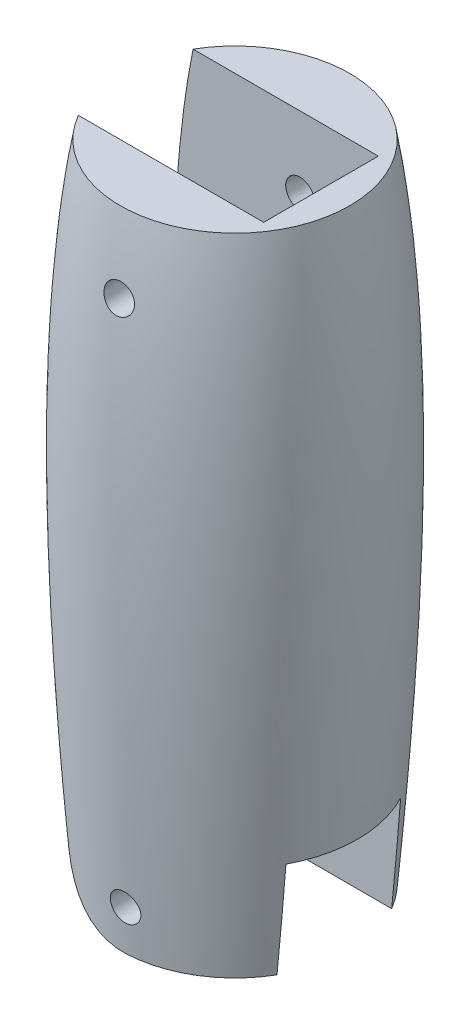
SolidWorks part; units mm, degrees
ref_plane "Front Plane" through (0, 0, 0) normal (0, 0, 1) x (1, 0, 0)
ref_plane "Top Plane" through (0, 0, 0) normal (0, 1, 0) x (1, 0, 0)
ref_plane "Right Plane" through (0, 0, 0) normal (1, 0, 0) x (0, 0, -1)
sketch "Sketch1" plane through (0, 0, 0) normal (1, 0, 0) x (0, 0, -1)
  line L0 (0, 22.5) -> (0, -22.5)
  line L1 (0, 22.5) -> (8, 22.5)
  line L2 (0, -22.5) -> (8, -22.5)
  line L3 (13.2094, -7.0442) -> (2.7906, 52.0442) construction
  spline S0 degree 2 poles (8, 22.5) (10.6047, 7.7279) (8, -22.5) knots 0 0 0 1 1 1
  point P3 (0, 0)
  dimension "D3" = 100
  dimension "D4" = 30
  dimension "D1" = 45
  dimension "D2" = 8
revolve "Revolve1" add sketch "Sketch1" angle 360 about L0
sketch "Sketch2" plane through (0, 0, 0) normal (1, 0, 0) x (0, 0, -1)
  line L0 (8, 22.5) -> (-8, 22.5) construction
  line L1 (-4, 9.5) -> (4, 9.5)
  line L2 (-4, 9.5) -> (-4, 22.5)
  line L3 (-4, 22.5) -> (4, 22.5)
  line L4 (4, 9.5) -> (4, 22.5)
  line L5 (-8, -22.5) -> (8, -22.5) construction
  line L6 (-4, -22.5) -> (4, -22.5)
  line L7 (-4, -22.5) -> (-4, -10.5)
  line L8 (-4, -10.5) -> (4, -10.5)
  line L9 (4, -22.5) -> (4, -10.5)
  point P12 (0, -10.5)
  point P14 (0, 9.5)
  dimension "D1" = 8
  dimension "D2" = 12
  dimension "D3" = 13
extrude "Cut-Extrude1" cut sketch "Sketch2" against normal through all and the other way blind 6
sketch "Sketch3" plane through (0, 0, 0) normal (0, 0, 1) x (1, 0, 0)
  line L0 (0.5359, -22.5) -> (0.5359, -19.5) construction
  line L1 (-6.9282, -22.5) -> (8, -22.5) construction
  line L2 (0.5359, 22.5) -> (0.5359, 17.5) construction
  line L3 (8, 22.5) -> (-6.9282, 22.5) construction
  circle A0 centre (0.5359, 17.5) radius 1
  circle A1 centre (0.5359, -19.5) radius 1
  dimension "D3" = 2
  dimension "D1" = 3
  dimension "D2" = 5
extrude "Cut-Extrude2" cut sketch "Sketch3" against normal through all and the other way through all
sketch "Sketch5" plane through (0, 0, 0) normal (0, 0, 1) x (1, 0, 0)
  line L2 (-6.9282, -22.5) -> (8, -22.5) construction
  line L3 (-6.9282, -22.5) -> (8, -22.5)
  line L4 (8, 22.5) -> (-6.9282, 22.5) construction
  line L5 (8, 22.5) -> (-6.9282, 22.5)
  arc A0 (-7.9472, 15.2138) -> (0.0209, 22.5) centre (0.0209, 14.5) cw
  arc A1 (0.9285, 22.5) -> (8.9036, 15.1307) centre (0.9285, 14.5) cw
  arc A2 (-7.5842, -15.1207) -> (0.3916, -22.5) centre (0.3916, -14.5) ccw
  spline S0 degree 2 poles (-501.1698, -1956.0965) (648.0055, 1954.765) (-789.8436, -1809.749) knots -9.398976 -9.398976 -9.398976 12.885608 12.885608 12.885608 only from (8, -22.5) to (8, 22.5) construction
  spline S1 degree 3 poles (1845.8539, 680.6997) (-1962.1388, -30.0919) (1945.6148, -109.903) (-1797.8674, -815.4189) knots -44.668115 -44.668115 -44.668115 -44.668115 54.513704 54.513704 54.513704 54.513704 only from (-7.9095, -10.5) to (-6.9282, -22.5) construction
  spline S3 degree 3 poles (-7.9095, -10.5) (-7.658, -14.5062) (-7.3256, -18.5058) (-6.9282, -22.5) knots 0 0 0 0 1 1 1 1
  spline S4 degree 3 poles (1845.8539, 680.6997) (-1962.1388, -30.0919) (1945.6148, -109.903) (-1797.8674, -815.4189) knots -44.668115 -44.668115 -44.668115 -44.668115 54.513704 54.513704 54.513704 54.513704 only from (-7.9095, -10.5) to (-6.9282, -22.5) construction
  spline S5 degree 3 poles (-7.9095, -10.5) (-7.658, -14.5062) (-7.3256, -18.5058) (-6.9282, -22.5) knots 0 0 0 0 1 1 1 1
  spline S6 degree 3 poles (-1999.434, -65.0382) (131.4144, -192.7145) (-17.3547, -79.9996) (-7.7636, 17.1112) (-7.6361, 18.1931) (0.9101, 77.9576) (88.0175, 128.3423) (1990.3265, -12.6904) knots -21.644551 -21.644551 -21.644551 -21.644551 0.5 0.5 0.75 0.75 14.345811 14.345811 14.345811 14.345811 only from (-8.2991, 9.5) to (-6.9282, 22.5) construction
  spline S7 degree 2 poles (8, -22.5) (10.6047, 7.7279) (8, 22.5) knots 0 0 0 1 1 1
  spline S8 degree 3 poles (-8.2991, 9.5) (-8.2182, 11.6822) (-8.0848, 13.8589) (-7.7636, 17.1112) (-7.6361, 18.1931) (-7.3275, 20.3513) (-7.1465, 21.4276) (-6.9282, 22.5) knots 0 0 0 0 0.5 0.5 0.75 0.75 1 1 1 1
  dimension "D1" = 8
  dimension "D2" = 8
extrude "Cut-Extrude4" cut sketch "Sketch5" against normal blind 20 from offset 10 contours A2 S5 L3 region at (-5.4723, -20.874, 0)
sketch "Sketch7" plane through (0, 9.5, 0) normal (0, 1, 0) x (1, 0, 0)
  circle A0 centre (-3, 0) radius 0.5
  circle A1 centre (4, 0) radius 0.5
  dimension "D1" = 1
  dimension "D2" = 1
  dimension "D3" = 3
  dimension "D4" = 4
extrude "Cut-Extrude5" cut sketch "Sketch7" against normal through all
sketch "Sketch8" plane through (6, 0, 0) normal (-1, 0, 0) x (0, 0, 1)
  line L0 (3.9999, -15.1207) -> (4, -22.5) construction
  line L1 (-4, -22.5) -> (3.9999, -22.5)
  line L2 (-4, -22.5) -> (-4, -15.5)
  line L3 (-4, -15.5) -> (3.9999, -15.5)
  line L4 (3.9999, -22.5) -> (3.9999, -15.5)
  dimension "D1" = 7
extrude "Cut-Extrude6" cut sketch "Sketch8" against normal through all
